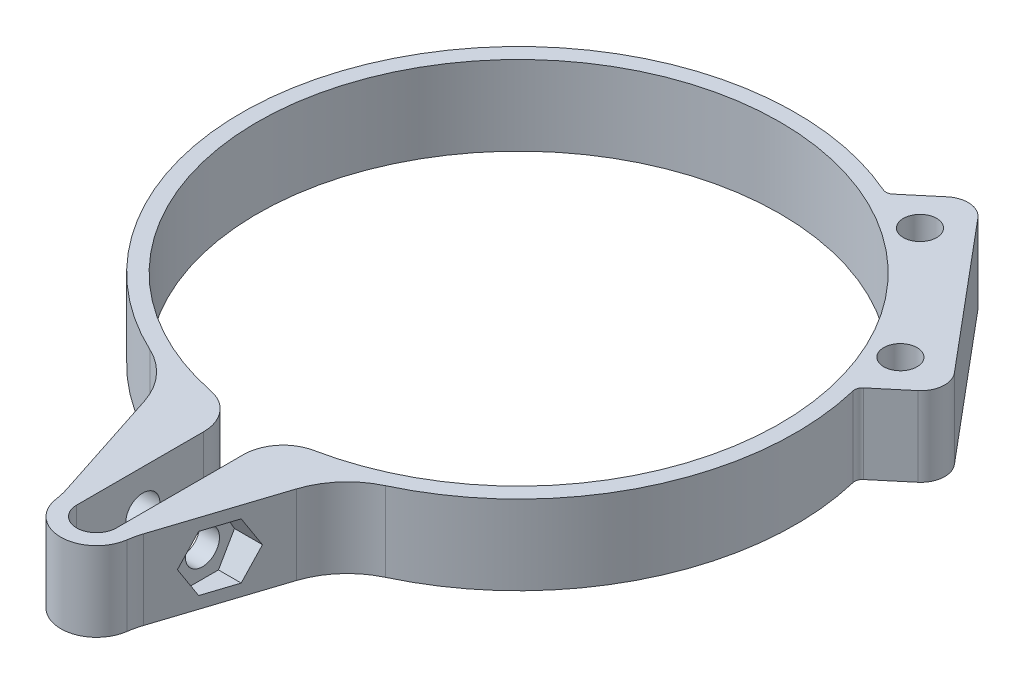
SolidWorks part; units mm, degrees
ref_plane "Front Plane" through (0, 0, 0) normal (0, 0, 1) x (1, 0, 0)
ref_plane "Top Plane" through (0, 0, 0) normal (0, 1, 0) x (1, 0, 0)
ref_plane "Right Plane" through (0, 0, 0) normal (1, 0, 0) x (0, 0, -1)
sketch "Sketch1" plane through (0, 0, 0) normal (0, 1, 0) x (1, 0, 0)
  line L0 (0, 0) -> (44.0628, 36.973) construction
  line L1 (22.9283, 34.904) -> (38.3552, 16.519)
  line L2 (18.7018, 35.2738) -> (14.9811, 32.1518)
  line L4 (37.9855, 12.2925) -> (34.2647, 9.1704)
  line L5 (-2.5, -37.1556) -> (-2.5, -53.1556)
  line L11 (-4.8483, -52.0837) -> (-9.5671, -37.5608)
  line L12 (2.5, -37.1556) -> (2.5, -53.1556)
  line L13 (0, -33.8126) -> (0, -59.9533) construction
  line L15 (4.8483, -52.0837) -> (9.5671, -37.5608)
  line L16 (20.3837, 30.158) -> (33.2394, 14.8371) construction
  line L17 (0, 0) -> (32.905, 0) construction
  arc A0 (6.5107, -32.2545) -> (-6.5107, -32.2545) centre (0, 0) ccw
  arc A1 (13.939, 32.001) -> (-14.8292, -31.5983) centre (0, 0) ccw
  arc A2 (14.8292, -31.5983) -> (33.9353, 8.1703) centre (0, 0) ccw
  arc A3 (-4.4562, -53.782) -> (0, -57.6556) centre (0, -53.1556) ccw
  arc A4 (-2.5, -53.1556) -> (2.5, -53.1556) centre (0, -53.1556) ccw
  arc A5 (4.4562, -53.782) -> (0, -57.6556) centre (0, -53.1556) cw
  arc A6 (-9.5671, -37.5608) -> (-14.8292, -31.5983) centre (-19.0776, -40.651) ccw
  arc A7 (-4.4562, -53.782) -> (-4.8483, -52.0837) centre (-14.3589, -55.1739) ccw
  arc A8 (4.4562, -53.782) -> (4.8483, -52.0837) centre (14.3589, -55.1739) cw
  arc A9 (9.5671, -37.5608) -> (14.8292, -31.5983) centre (19.0776, -40.651) cw
  arc A10 (6.5107, -32.2545) -> (2.5, -37.1556) centre (7.5, -37.1556) ccw
  arc A11 (-2.5, -37.1556) -> (-6.5107, -32.2545) centre (-7.5, -37.1556) ccw
  circle A12 centre (20.3837, 30.158) radius 2.1
  circle A13 centre (33.2394, 14.8371) radius 2.1
  arc A14 (38.3552, 16.519) -> (37.9855, 12.2925) centre (36.0571, 14.5906) cw
  arc A15 (22.9283, 34.904) -> (18.7018, 35.2738) centre (20.6302, 32.9757) ccw
  arc A16 (33.9353, 8.1703) -> (34.2647, 9.1704) centre (34.9075, 8.4044) cw
  arc A17 (13.939, 32.001) -> (14.9811, 32.1518) centre (14.3383, 32.9178) ccw
  point P20 (-11.0088, -33.1235)
  point P30 (-4.5, -53.1556)
  point P33 (4.5, -53.1556)
  point P36 (11.0088, -33.1235)
  dimension "D1" = 65.81
  dimension "D4" = 10
  dimension "D5" = 5
  dimension "D6" = 4.2
  dimension "D10" = 3
  dimension "D11" = 1
  dimension "D16" = 2.5
  dimension "D2" = 2
  dimension "D3" = 5
  dimension "D7" = 5
  dimension "D9" = 40
  dimension "D13" = 20
  dimension "D8" = 5
  dimension "D12" = 18
  dimension "D14" = 2
  dimension "D15" = 16
  dimension "D17" = 30
  dimension "D18" = 40
extrude "Boss-Extrude1" add sketch "Sketch1" along normal blind 10 contours A5 L15 A2 L4 L1 L2 A1 L11 A3 A4 A0 region at (29.7277, 0, -24.9445)
sketch "Sketch3" plane through (0, 0, 0) normal (1, 0, 0) x (0, 0, -1)
  line L0 (-44.8223, 10) -> (-44.8223, 0) construction
  line L1 (-52.0837, 10) -> (-37.5608, 10) construction
  line L2 (-52.0837, 0) -> (-37.5608, 0) construction
  circle A0 centre (-44.8223, 5) radius 2.15
  dimension "D1" = 4.3
extrude "Cut-Extrude1" cut sketch "Sketch3" against normal blind 10 and the other way blind 10
sketch "Sketch4" plane through (0, 0, 0) normal (1, 0, 0) x (0, 0, -1)
  circle A0 centre (-44.8223, 5) radius 3.75
  dimension "D1" = 7.5
extrude "Cut-Extrude2" cut sketch "Sketch4" against normal blind 10 from offset 6 offset against normal yes
sketch "Sketch5" plane through (2.5, 0, 0) normal (-1, 0, 0) x (0, 0, 1)
  line L0 (52.0837, 0) -> (37.5608, 0) construction
  line L1 (46.843, 8.5) -> (42.8015, 8.5)
  line L2 (42.8015, 8.5) -> (40.7808, 5)
  line L3 (40.7808, 5) -> (42.8015, 1.5)
  line L4 (42.8015, 1.5) -> (46.843, 1.5)
  line L5 (46.843, 1.5) -> (48.8637, 5)
  line L6 (48.8637, 5) -> (46.843, 8.5)
  circle A0 centre (44.8223, 5) radius 3.5 construction
  dimension "D1" = 7
extrude "Cut-Extrude3" cut sketch "Sketch5" against normal blind 10 from offset 2.5 offset against normal yes
equation "\"D16@Sketch1\"=\"D3@Sketch1\"/2"
